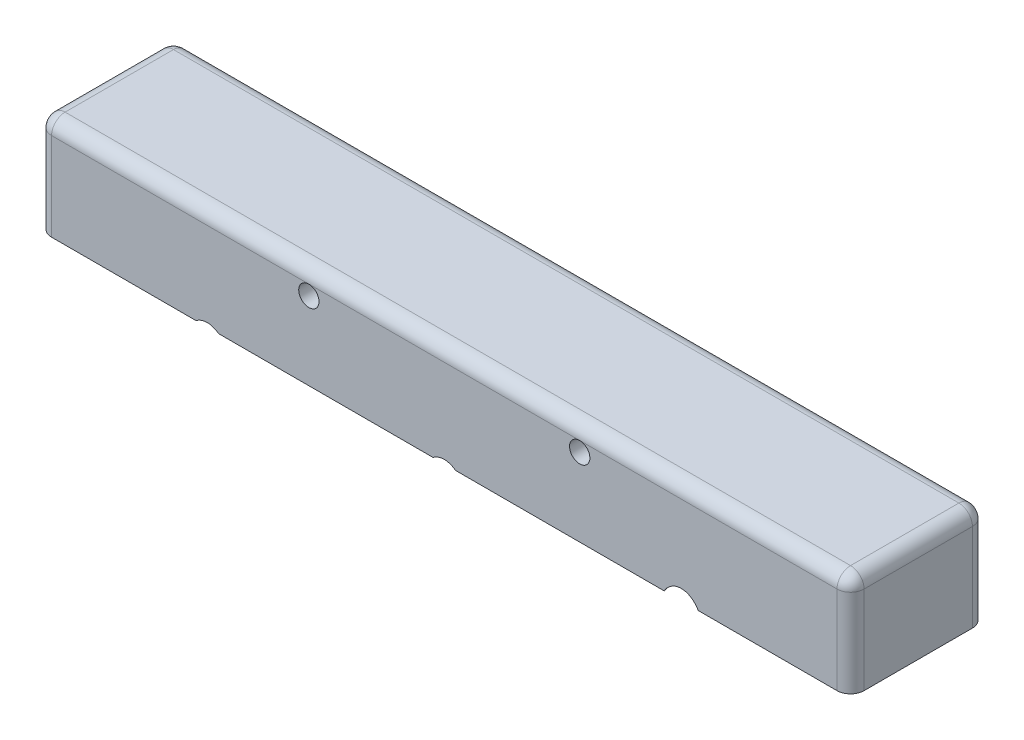
SolidWorks part; units mm, degrees
ref_plane "Front Plane" through (0, 0, 0) normal (0, 0, 1) x (1, 0, 0)
ref_plane "Top Plane" through (0, 0, 0) normal (0, 1, 0) x (1, 0, 0)
ref_plane "Right Plane" through (0, 0, 0) normal (1, 0, 0) x (0, 0, -1)
sketch "Sketch1" plane through (0, 0, 0) normal (0, 1, 0) x (1, 0, 0)
  line L1 (60, -7.5) -> (-60, -7.5)
  line L2 (60, -7.5) -> (60, 7.5)
  line L3 (60, 7.5) -> (-60, 7.5)
  line L4 (-60, -7.5) -> (-60, 7.5)
  line L5 (60, -7.5) -> (-60, 7.5) construction
  line L6 (60, 7.5) -> (-60, -7.5) construction
  point P0 (0, 0)
  dimension "D1" = 120
  dimension "D2" = 15
extrude "Boss-Extrude1" add sketch "Sketch1" along normal blind 15
sketch "Sketch2" plane through (-60, 0, 0) normal (-1, 0, 0) x (0, 0, 1)
  circle A0 centre (0, 0) radius 6
  dimension "D1" = 12
extrude "Cut-Extrude4" cut sketch "Sketch2" against normal offset from surface (114 mm away) 3 from offset 3 up to face at (60, 7.5, 0) offset against normal yes
sketch "Sketch3" plane through (0, 0, 7.5) normal (0, 0, 1) x (1, 0, 0)
  line L1 (-60, 15) -> (60, 15)
  line L2 (-60, 15) -> (-60, 0)
  line L3 (-60, 0) -> (60, 0)
  line L4 (60, 15) -> (60, 0)
extrude "Boss-Extrude2" add sketch "Sketch3" along normal blind 5
ref_plane "Plane1" through (0, -5.4127, 9.375) normal (0, -0.5, 0.866) x (1, 0, 0)
sketch "Sketch5" plane through (0, -5.4127, 9.375) normal (0, -0.5, 0.866) x (1, 0, 0)
  line L0 (-60, -3.75) -> (-60, 6.25) construction
  line L1 (60, 6.25) -> (60, -3.75) construction
  line L2 (0, 6.25) -> (0, -18.0969) construction
  line L3 (-60, 6.25) -> (60, 6.25) construction
  circle A0 centre (-35, 3.75) radius 3
  circle A1 centre (0, 3.75) radius 3
  circle A2 centre (35, 4.6104) radius 3
  dimension "D1" = 6
  dimension "D2" = 25
  dimension "D3" = 25
  dimension "D4" = 2.5
extrude "Cut-Extrude5" cut sketch "Sketch5" against normal blind 11
sketch "Sketch6" plane through (0, 0, 12.5) normal (0, 0, 1) x (1, 0, 0)
  line L0 (-60, 15) -> (-60, 0) construction
  line L1 (60, 0) -> (60, 15) construction
  line L2 (60, 15) -> (-60, 15) construction
  circle A0 centre (-20, 11.5) radius 1.5
  circle A1 centre (20, 11.5) radius 1.5
  dimension "D1" = 3
  dimension "D2" = 40
  dimension "D3" = 40
  dimension "D4" = 3.5
extrude "Cut-Extrude6" cut sketch "Sketch6" against normal through all
fillet "Fillet2" radius 2 1 edges at (0, 15, -7.5) type face fillet first side face at (21.5, 11.5, -7.5) second side face at (0, 15, 2.5)
fillet "Fillet3" radius 2 1 edges at (0, 15, 12.5) type face fillet first side face at (21.5, 11.5, 12.5) second side face at (0, 15, 3.5)
fillet "Fillet4" radius 2 3 edges at (-60, 6.5, 12.5) (-60, 15, 2.5) (-60, 6.5, -7.5) type face fillet first side face at (-60, 9.4714, 2.5) second side face at (0.2143, 5.5518, 12.5) second side face at (0, 15, 2.5) second side face at (0.375, 9.375, -7.5)
fillet "Fillet5" radius 2 3 edges at (60, 15, 2.5) (60, 6.5, 12.5) (60, 6.5, -7.5) type face fillet first side face at (60, 9.4714, 2.5) second side face at (0.875, 9.375, -7.5) second side face at (1, 15, 2.5) second side face at (0.5, 5.5518, 12.5)
